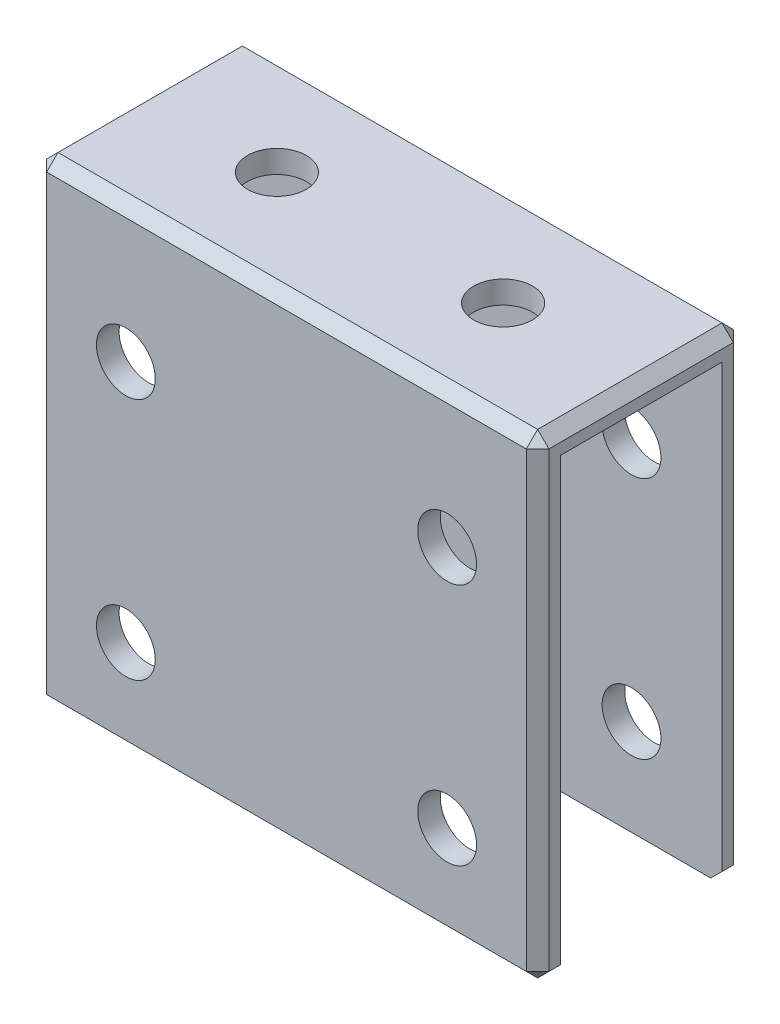
SolidWorks part; units mm, degrees
ref_plane "Front Plane" through (0, 0, 0) normal (0, 0, 1) x (1, 0, 0)
ref_plane "Top Plane" through (0, 0, 0) normal (0, 1, 0) x (1, 0, 0)
ref_plane "Right Plane" through (0, 0, 0) normal (1, 0, 0) x (0, 0, -1)
sketch "Sketch1" plane through (0, 0, 0) normal (0, 0, 1) x (1, 0, 0)
  line L0 (22.2, 40) -> (22.2, 0) construction
  line L1 (0, 0) -> (44.4, 0)
  line L2 (0, 0) -> (0, 40)
  line L3 (0, 40) -> (44.4, 40)
  line L4 (44.4, 0) -> (44.4, 40)
  line L5 (0, 0) -> (8, 0) construction
  line L6 (0, 0) -> (0, 8) construction
  line L10 (8, 29.9769) -> (8, 27.3769) construction
  line L11 (8, 19) -> (8, 8.4769) construction
  line L12 (8, 19) -> (10.573, 19) construction
  line L15 (10.573, 19) -> (10.573, 40) construction
  line L16 (8, 8.4769) -> (36.4, 8.4769) construction
  line L17 (36.4, 8.4769) -> (36.4, 29.9769) construction
  circle A0 centre (8, 8.4769) radius 2.6
  circle A1 centre (8, 29.9769) radius 2.6
  circle A2 centre (36.4, 29.9769) radius 2.6
  circle A3 centre (36.4, 8.4769) radius 2.6
  dimension "D5" = 5.2
  dimension "D6" = 5.2
  dimension "D7" = 5.2
  dimension "D8" = 5.2
  dimension "D1" = 44.4
  dimension "D2" = 40
  dimension "D3" = 21.5
  dimension "D4" = 21.5
  dimension "D9" = 21
  dimension "D10" = 8
  dimension "D11" = 8
extrude "Boss-Extrude1" add sketch "Sketch1" along normal blind 2
sketch "Sketch2" plane through (0, 40, 0) normal (0, 1, 0) x (1, 0, 0)
  line L0 (44.4, -2) -> (44.4, 0) construction
  line L1 (0, -2) -> (44.4, -2)
  line L2 (0, -2) -> (0, 16.3)
  line L3 (0, 16.3) -> (44.4, 16.3)
  line L4 (44.4, -2) -> (44.4, 16.3)
  dimension "D1" = 18.3
  dimension "D2" = 44.4
extrude "Boss-Extrude2" add sketch "Sketch2" along normal blind 2
pattern_linear "LPattern1" count 2 spacing 16.3 along (0, 0, -1) of "Boss-Extrude1"
sketch "Sketch3" plane through (0, 42, 0) normal (0, 1, 0) x (1, 0, 0)
  line L0 (22.2, 16.3) -> (22.2, -2) construction
  line L1 (44.4, 16.3) -> (0, 16.3) construction
  line L2 (0, -2) -> (44.4, -2) construction
  line L3 (22.2, 7.15) -> (12.2, 7.15) construction
  line L4 (22.2, 7.15) -> (32.2, 7.15) construction
  circle A0 centre (12.2, 7.15) radius 2.6
  circle A1 centre (32.2, 7.15) radius 2.6
  dimension "D3" = 5.2
  dimension "D4" = 5.2
  dimension "D1" = 10
  dimension "D2" = 10
extrude "Cut-Extrude1" cut sketch "Sketch3" against normal through all
chamfer "Chamfer1" distance 1 angle 45 14 edges at (22.2, 42, -16.3) (0, 42, -7.15) (0, 21, -16.3) (22.2, 42, 2) (0, 21, 2) (0, 0, -15.3) (0, 0, 1) (22.2, 0, 2) (44.4, 0, 1) (44.4, 21, 2) (44.4, 42, -7.15) (44.4, 21, -16.3) (44.4, 0, -15.3) (22.2, 0, -16.3)
